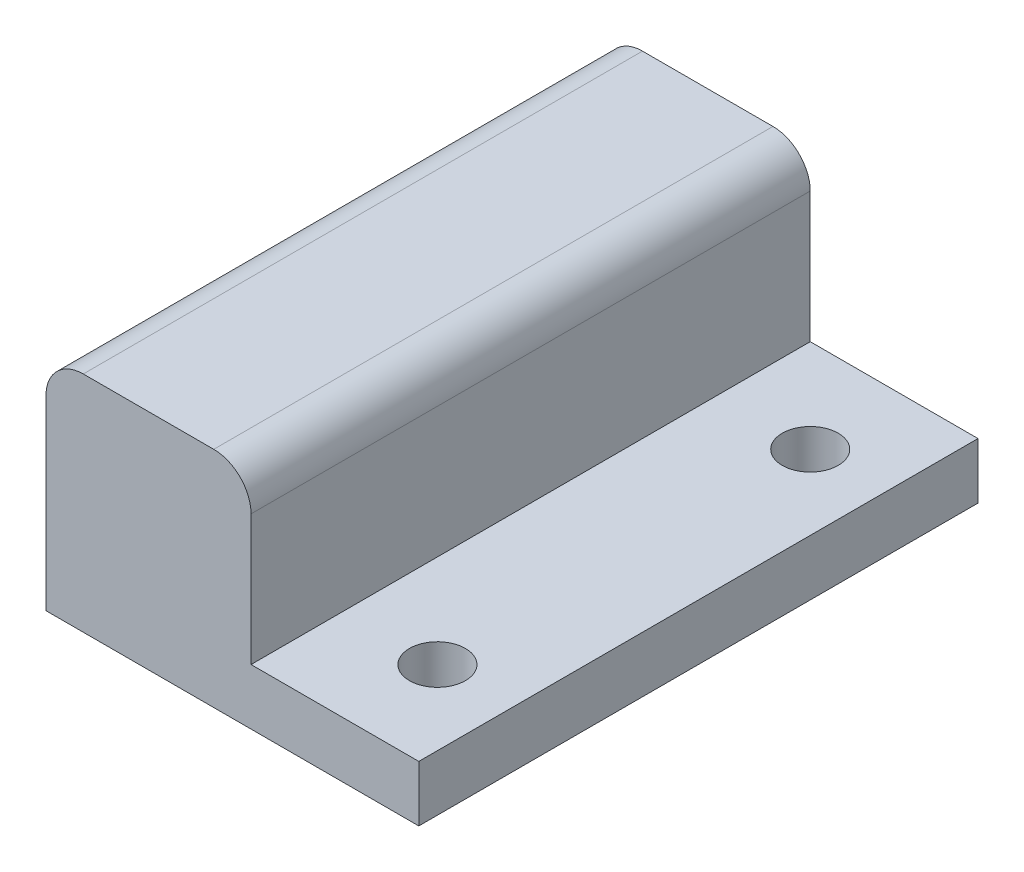
SolidWorks part; units mm, degrees
ref_plane "Front Plane" through (0, 0, 0) normal (0, 0, 1) x (1, 0, 0)
ref_plane "Top Plane" through (0, 0, 0) normal (0, 1, 0) x (1, 0, 0)
ref_plane "Right Plane" through (0, 0, 0) normal (1, 0, 0) x (0, 0, -1)
sketch "Sketch1" plane through (0, 0, 0) normal (0, 1, 0) x (1, 0, 0)
  line L0 (0, 0) -> (0, -25.4) construction
  line L1 (-20.32, 6.35) -> (5.08, 6.35)
  line L2 (-20.32, 6.35) -> (-20.32, -31.75)
  line L3 (-20.32, -31.75) -> (5.08, -31.75)
  line L4 (5.08, 6.35) -> (5.08, -31.75)
  circle A0 centre (0, 0) radius 1.905
  circle A1 centre (0, -25.4) radius 1.905
  point P6 (-20.32, -12.7)
  point P12 (0, -12.7)
  dimension "D1" = 25.4
  dimension "D2" = 3.81
  dimension "D3" = 3.81
  dimension "D4" = 5.08
  dimension "D5" = 38.1
  dimension "D6" = 25.4
extrude "Boss-Extrude1" add sketch "Sketch1" along normal blind 3.81
sketch "Sketch2" plane through (0, 3.81, 0) normal (0, 1, 0) x (1, 0, 0)
  line L0 (-20.32, 6.35) -> (-20.32, -31.75)
  line L1 (-20.32, -31.75) -> (-6.35, -31.75)
  line L2 (-20.32, -31.75) -> (5.08, -31.75) construction
  line L3 (-6.35, -31.75) -> (-6.35, 6.35)
  line L4 (5.08, 6.35) -> (-20.32, 6.35) construction
  line L5 (-6.35, 6.35) -> (-8.89, 6.35)
  line L6 (-8.89, 6.35) -> (-8.89, -29.21)
  line L7 (-8.89, -29.21) -> (-17.78, -29.21)
  line L8 (-17.78, -29.21) -> (-17.78, 6.35)
  line L9 (-17.78, 6.35) -> (-20.32, 6.35)
  dimension "D1" = 2.54
  dimension "D2" = 8.89
  dimension "D3" = 2.54
extrude "Boss-Extrude2" add sketch "Sketch2" along normal blind 8.89 contours L0 L1 L3 L5 L6 L7 L8 L9
sketch "Sketch3" plane through (0, 12.7, 0) normal (0, 1, 0) x (1, 0, 0)
  line L1 (-20.32, 6.35) -> (-6.35, 6.35)
  line L2 (-20.32, 6.35) -> (-20.32, -31.75)
  line L3 (-20.32, -31.75) -> (-6.35, -31.75)
  line L4 (-6.35, 6.35) -> (-6.35, -31.75)
extrude "Boss-Extrude3" add sketch "Sketch3" along normal blind 2.54
chamfer "Chamfer1" distance 1.27 angle 45 2 edges at (-8.89, 12.7, 11.43) (-17.78, 12.7, 11.43)
fillet "Fillet2" radius 2.54 2 edges at (-6.35, 15.24, 12.7) (-20.32, 15.24, 12.7)
